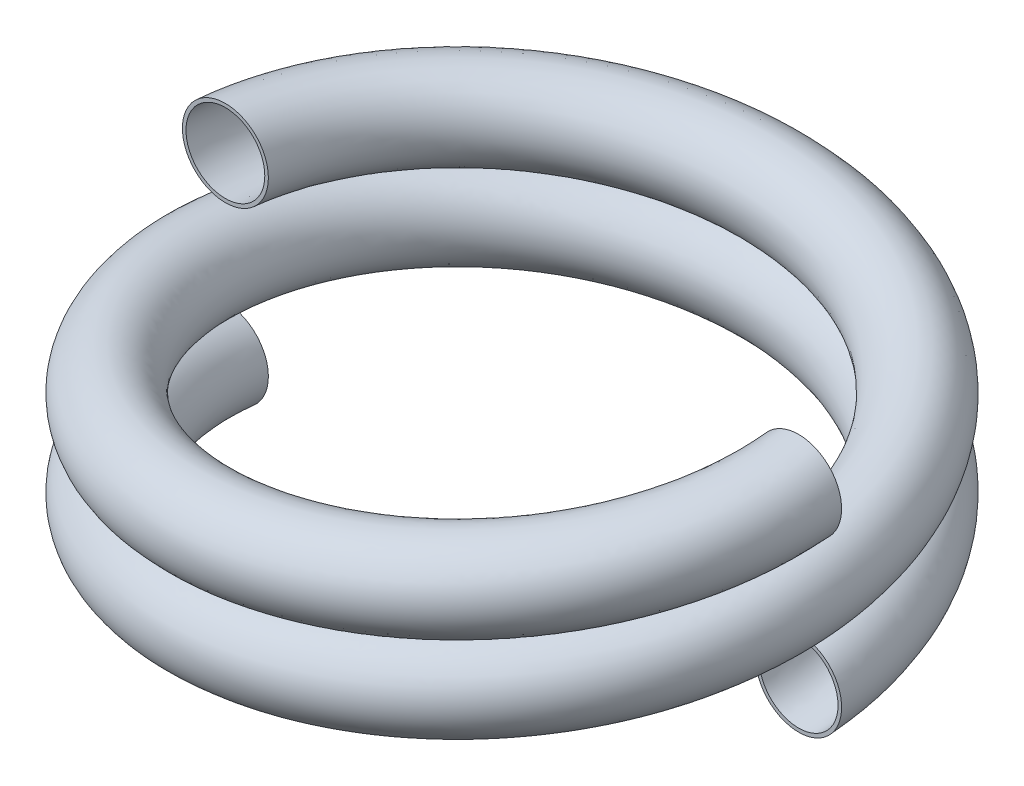
SolidWorks part; units mm, degrees
note: '?' marks a value the reader was unsure of.
material "7075-T6 (SN)"
ref_plane "Front Plane" through (0, 0, 0) normal (0, 0, 1) x (1, 0, 0)
ref_plane "Top Plane" through (0, 0, 0) normal (0, 1, 0) x (1, 0, 0)
ref_plane "Right Plane" through (0, 0, 0) normal (1, 0, 0) x (0, 0, -1)
ref_axis "Axis1" through (0, 807.72, 0) along (0, -1, 0)?
sketch "Sketch2" plane through (0, 0, 0) normal (0, 1, 0) x (1, 0, 0)
  circle A0 centre (0, 0) radius 1016
  dimension "D1" = 2032
curve "Helix/Spiral1" pitch 609.6 height 609.6 radius 1016 centre (0, 0, 0) axis (0, 1, 0) start towards (0, 0, 1)
sketch "Sketch3" plane through (0, 0, 0) normal (0, 1, 0) x (1, 0, 0)
  circle A0 centre (0, 0) radius 1016 construction
  circle A1 centre (0, 0) radius 1016
curve "Helix/Spiral2" pitch 609.6 height 609.6 radius 1016 centre (0, 0, 0) axis (0, 1, 0) start towards (1, 0, 0)
sketch "Sketch4" plane through (0, 0, 0) normal (0, 0, 1) x (1, 0, 0)
  circle A0 centre (1016, 0) radius 139.7
  circle A2 centre (1016, 0) radius 152.4
  spline S0 degree 3 poles (1016, 0) (1016, 1.441) (1015.3274, 4.3235) (1012.3026, 8.6468) (1007.268, 12.9702) (1000.2336, 17.2936) (991.2133, 21.617) (980.225, 25.9404) (967.2906, 30.2638) (952.4358, 34.5872) (935.6899, 38.9106) (917.0863, 43.234) (896.662, 47.5574) (874.4574, 51.8809) (850.5166, 56.2043) (824.8872, 60.5277) (797.6201, 64.8511) (768.7694, 69.1745) (738.3924, 73.4979) (706.5493, 77.8213) (673.3035, 82.1447) (638.7209, 86.4681) (602.8701, 90.7915) (565.8224, 95.1149) (527.6514, 99.4383) (488.4327, 103.7617) (448.2443, 108.0851) (407.1659, 112.4085) (365.2792, 116.7319) (322.6672, 121.0553) (279.4146, 125.3787) (235.6072, 129.7021) (191.3321, 134.0255) (146.6771, 138.3489) (101.7309, 142.6723) (56.5827, 146.9957) (11.3222, 151.3191) (-33.9609, 155.6426) (-79.1764, 159.966) (-124.2348, 164.2894) (-169.0466, 168.6128) (-213.5227, 172.9362) (-257.5748, 177.2596) (-301.1156, 181.583) (-344.0586, 185.9064) (-386.3184, 190.2298) (-427.8113, 194.5532) (-468.4548, 198.8766) (-508.1682, 203.2) (-546.8726, 207.5234) (-584.4913, 211.8468) (-620.9496, 216.1702) (-656.175, 220.4936) (-690.0977, 224.817) (-722.6502, 229.1404) (-753.768, 233.4638) (-783.3892, 237.7872) (-811.4551, 242.1106) (-837.9099, 246.434) (-862.7011, 250.7574) (-885.7795, 255.0809) (-907.0993, 259.4043) (-926.6181, 263.7277) (-944.2972, 268.0511) (-960.1015, 272.3745) (-973.9996, 276.6979) (-985.9639, 281.0213) (-995.9707, 285.3447) (-1004, 289.6681) (-1010.036, 293.9915) (-1014.0667, 298.3149) (-1016.084, 302.6383) (-1016.084, 306.9617) (-1014.0667, 311.2851) (-1010.036, 315.6085) (-1004, 319.9319) (-995.9707, 324.2553) (-985.9639, 328.5787) (-973.9996, 332.9021) (-960.1015, 337.2255) (-944.2972, 341.5489) (-926.6181, 345.8723) (-907.0993, 350.1957) (-885.7795, 354.5191) (-862.7011, 358.8426) (-837.9099, 363.166) (-811.4551, 367.4894) (-783.3892, 371.8128) (-753.768, 376.1362) (-722.6502, 380.4596) (-690.0977, 384.783) (-656.175, 389.1064) (-620.9496, 393.4298) (-584.4913, 397.7532) (-546.8726, 402.0766) (-508.1682, 406.4) (-468.4548, 410.7234) (-427.8113, 415.0468) (-386.3184, 419.3702) (-344.0586, 423.6936) (-301.1156, 428.017) (-257.5748, 432.3404) (-213.5227, 436.6638) (-169.0466, 440.9872) (-124.2348, 445.3106) (-79.1764, 449.634) (-33.9609, 453.9574) (11.3222, 458.2809) (56.5827, 462.6043) (101.7309, 466.9277) (146.6771, 471.2511) (191.3321, 475.5745) (235.6072, 479.8979) (279.4146, 484.2213) (322.6672, 488.5447) (365.2792, 492.8681) (407.1659, 497.1915) (448.2443, 501.5149) (488.4327, 505.8383) (527.6514, 510.1617) (565.8224, 514.4851) (602.8701, 518.8085) (638.7209, 523.1319) (673.3035, 527.4553) (706.5493, 531.7787) (738.3924, 536.1021) (768.7694, 540.4255) (797.6201, 544.7489) (824.8872, 549.0723) (850.5166, 553.3957) (874.4574, 557.7191) (896.662, 562.0426) (917.0863, 566.366) (935.6899, 570.6894) (952.4358, 575.0128) (967.2906, 579.3362) (980.225, 583.6596) (991.2133, 587.983) (1000.2336, 592.3064) (1007.268, 596.6298) (1012.3026, 600.9532) (1015.3274, 605.2765) (1016, 608.159) (1016, 609.6) knots 0 0 0 0 0.007092 0.014184 0.021277 0.028369 0.035461 0.042553 0.049645 0.056738 0.06383 0.070922 0.078014 0.085106 0.092199 0.099291 0.106383 0.113475 0.120567 0.12766 0.134752 0.141844 0.148936 0.156028 0.163121 0.170213 0.177305 0.184397 0.191489 0.198582 0.205674 0.212766 0.219858 0.22695 0.234043 0.241135 0.248227 0.255319 0.262411 0.269504 0.276596 0.283688 0.29078 0.297872 0.304965 0.312057 0.319149 0.326241 0.333333 0.340426 0.347518 0.35461 0.361702 0.368794 0.375887 0.382979 0.390071 0.397163 0.404255 0.411348 0.41844 0.425532 0.432624 0.439716 0.446809 0.453901 0.460993 0.468085 0.475177 0.48227 0.489362 0.496454 0.503546 0.510638 0.51773 0.524823 0.531915 0.539007 0.546099 0.553191 0.560284 0.567376 0.574468 0.58156 0.588652 0.595745 0.602837 0.609929 0.617021 0.624113 0.631206 0.638298 0.64539 0.652482 0.659574 0.666667 0.673759 0.680851 0.687943 0.695035 0.702128 0.70922 0.716312 0.723404 0.730496 0.737589 0.744681 0.751773 0.758865 0.765957 0.77305 0.780142 0.787234 0.794326 0.801418 0.808511 0.815603 0.822695 0.829787 0.836879 0.843972 0.851064 0.858156 0.865248 0.87234 0.879433 0.886525 0.893617 0.900709 0.907801 0.914894 0.921986 0.929078 0.93617 0.943262 0.950355 0.957447 0.964539 0.971631 0.978723 0.985816 0.992908 1 1 1 1 construction
  dimension "D2" = 279.4
  dimension "D1" = 0
sweep "Sweep1" add profiles "Sketch4" path "Helix/Spiral2"
ref_plane "Plane1" through (0, -152.4, 0) normal (0, 1, 0) x (1, 0, 0)
sketch "Sketch5" plane through (0, 0, 0) normal (0, 0, 1) x (1, 0, 0)
  circle A0 centre (-1016, 0) radius 152.4
  circle A1 centre (-1016, 0) radius 139.7
  dimension "D1" = 304.8
  dimension "D2" = 279.4
sweep "Sweep4" add profiles "Sketch5" path "Helix/Spiral1"
